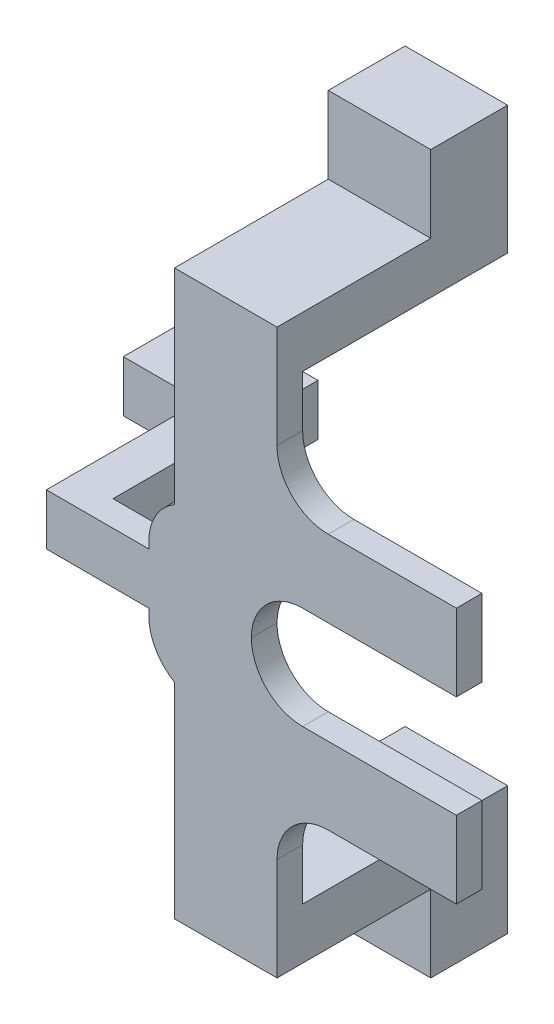
SolidWorks part; units mm, degrees
ref_plane "前视基准面" through (0, 0, 0) normal (0, 0, 1) x (1, 0, 0)
ref_plane "上视基准面" through (0, 0, 0) normal (0, 1, 0) x (1, 0, 0)
ref_plane "右视基准面" through (0, 0, 0) normal (1, 0, 0) x (0, 0, -1)
sketch "草图1" plane through (0, 0, 0) normal (0, 0, 1) x (1, 0, 0)
  line L4 (20, -10) -> (20, -0.4)
  line L5 (20, 10) -> (-20, 10)
  line L6 (-20, 10) -> (-20, 0.4)
  line L7 (-20, -10) -> (20, -10)
  line L8 (20, -0.4) -> (27, -0.4)
  line L9 (27, -0.4) -> (27, 0.4)
  line L10 (27, 0.4) -> (20, 0.4)
  line L11 (-27, -0.4) -> (-20, -0.4)
  line L12 (-27, 0.4) -> (-20, 0.4)
  line L13 (-20, 10) -> (20, -10)
  line L14 (20, 10) -> (-20, -10)
  line L15 (-27, 0.4) -> (-27, -0.4)
  line L16 (-20, -0.4) -> (-20, -10)
  line L17 (20, 0.4) -> (20, 10)
  line L19 (30, -15) -> (-30, -15)
  line L20 (30, -15) -> (30, 15)
  line L21 (30, 15) -> (-30, 15)
  line L22 (-30, -15) -> (-30, 15)
  line L23 (30, -15) -> (-30, 15) construction
  line L24 (30, 15) -> (-30, -15) construction
  point P0 (0, 0)
  point P1 (0, 0)
  dimension "D1" = 40
  dimension "D2" = 20
  dimension "D3" = 20
  dimension "D4" = 10
  dimension "D5" = 7
  dimension "D6" = 0.8
  dimension "D7" = 60
  dimension "D8" = 30
extrude "凸台-拉伸1" add sketch "草图1" along normal blind 5 contours L22 L19 L20 L21 L17 L10 L9 L8 L4 L7 L16 L11 L15 L12 L6 L5 region at (0, -14.3292, 0)
sketch "草图2" plane through (0, 0, 5) normal (0, 0, 1) x (1, 0, 0)
  line L0 (-27, 0.4) -> (-27, -0.4)
  line L1 (-27, -0.4) -> (-20, -0.4)
  line L2 (-20, -0.4) -> (-20, 0.4)
  line L3 (-20, 0.4) -> (-27, 0.4)
  line L12 (-19.8, 0.6) -> (-27.2, 0.6)
  line L13 (-27.2, 0.6) -> (-27.2, -0.6)
  line L14 (-27.2, -0.6) -> (-19.8, -0.6)
  line L15 (-19.8, -0.6) -> (-19.8, 0.6)
  line L16 (0, 0) -> (0, 5.1625) construction
  line L17 (19.8, -0.6) -> (19.8, 0.6)
  line L18 (27.2, -0.6) -> (19.8, -0.6)
  line L19 (27.2, 0.6) -> (27.2, -0.6)
  line L20 (19.8, 0.6) -> (27.2, 0.6)
  line L21 (20, 0.4) -> (27, 0.4)
  line L22 (20, -0.4) -> (20, 0.4)
  line L23 (27, -0.4) -> (20, -0.4)
  line L24 (27, 0.4) -> (27, -0.4)
  dimension "D1" = 0.2
extrude "切除-拉伸1" cut sketch "草图2" against normal blind 10
sketch "草图3" plane through (0, 0, 5) normal (0, 0, 1) x (1, 0, 0)
  line L0 (-20, 10) -> (-20, -10)
  line L1 (-20, -10) -> (20, -10)
  line L2 (20, -10) -> (20, 10)
  line L3 (20, 10) -> (-20, 10)
  line L4 (20.2, 10.2) -> (-20.2, 10.2)
  line L5 (-20.2, 10.2) -> (-20.2, -10.2)
  line L6 (-20.2, -10.2) -> (20.2, -10.2)
  line L7 (20.2, -10.2) -> (20.2, 10.2)
  dimension "D1" = 0.2
extrude "切除-拉伸2" cut sketch "草图3" against normal blind 10
sketch "草图5" plane through (0, 0, 0) normal (0, 0, -1) x (-1, 0, 0)
  line L0 (5, 15) -> (5, 55)
  line L1 (-30, 15) -> (30, 15) construction
  line L2 (30, -15) -> (30, 15) construction
  line L3 (30, 0) -> (44.4232, 0) construction
  line L4 (5, 55) -> (25, 55)
  line L6 (25, 55) -> (25, 15)
  line L7 (25, 15) -> (5, 15)
  line L8 (25, -15) -> (5, -15)
  line L9 (25, -55) -> (25, -15)
  line L10 (5, -55) -> (25, -55)
  line L11 (5, -15) -> (5, -55)
  line L12 (30, 0) -> (50, 0) construction
  line L13 (50, -5) -> (50, 5)
  line L14 (50, 5) -> (30, 5)
  line L15 (50, -5) -> (30, -5)
  line L16 (30, 5) -> (30, -5)
  point P18 (50, 0)
  dimension "D1" = 25
  dimension "D2" = 55
  dimension "D3" = 20
  dimension "D4" = 40
  dimension "D5" = 20
  dimension "D6" = 10
extrude "凸台-拉伸2" add sketch "草图5" against normal blind 5
sketch "草图6" plane through (0, 0, 0) normal (0, 0, -1) x (-1, 0, 0)
  line L0 (25, 15) -> (25, 55) construction
  line L1 (5, 55) -> (25, 55)
  line L2 (5, 55) -> (5, 45)
  line L3 (5, 45) -> (25, 45)
  line L4 (25, 55) -> (25, 45)
  line L5 (27.2, 0) -> (34.9251, 0) construction
  line L6 (27.2, 0.6) -> (27.2, -0.6) construction
  line L7 (25, -55) -> (25, -45)
  line L8 (5, -45) -> (25, -45)
  line L9 (5, -55) -> (5, -45)
  line L10 (5, -55) -> (25, -55)
  line L11 (25, 55) -> (5, 55) construction
  line L12 (50, 5) -> (50, -5)
  line L13 (50, -5) -> (50, 5) construction
  line L14 (50, 5) -> (30, 5) construction
  line L15 (50, -5) -> (42, -5)
  line L16 (30, -5) -> (50, -5) construction
  line L17 (42, -5) -> (42, 5)
  line L18 (42, 5) -> (50, 5)
  line L19 (5, -15) -> (5, -55) construction
  dimension "D1" = 90
  dimension "D2" = 8
extrude "凸台-拉伸3" add sketch "草图6" along normal blind 40
sketch "草图7" plane through (0, 0, -40) normal (0, 0, -1) x (-1, 0, 0)
  line L0 (27.2, 0) -> (32.2152, 0) construction
  line L1 (27.2, 0.6) -> (27.2, -0.6) construction
  line L2 (5, 55) -> (5, 70)
  line L3 (5, 70) -> (25, 70)
  line L4 (25, 70) -> (25, 55)
  line L5 (25, 45) -> (25, 55) construction
  line L6 (25, 55) -> (5, 55) construction
  line L7 (25, 55) -> (5, 55)
  line L8 (25, -55) -> (5, -55)
  line L9 (25, -70) -> (25, -55)
  line L10 (5, -70) -> (25, -70)
  line L11 (5, -55) -> (5, -70)
  line L12 (50, 5) -> (50, -5)
  line L13 (50, -5) -> (50, 5) construction
  line L14 (42, -5) -> (50, -5) construction
  line L15 (50, -5) -> (65, -5)
  line L16 (65, -5) -> (65, 5)
  line L17 (65, 5) -> (50, 5)
  line L18 (5, 55) -> (5, 45) construction
  dimension "D1" = 15
  dimension "D2" = 15
extrude "凸台-拉伸4" add sketch "草图7" against normal blind 15
sketch "草图8" plane through (0, 0, 5) normal (0, 0, 1) x (1, 0, 0)
  line L1 (27.466, -12.3413) -> (-27.466, -12.3413)
  line L2 (27.466, -12.3413) -> (27.466, 12.3413)
  line L3 (27.466, 12.3413) -> (-27.466, 12.3413)
  line L4 (-27.466, -12.3413) -> (-27.466, 12.3413)
  line L5 (27.466, -12.3413) -> (-27.466, 12.3413) construction
  line L6 (27.466, 12.3413) -> (-27.466, -12.3413) construction
  point P0 (0, 0)
extrude "凸台-拉伸5" add sketch "草图8" against normal blind 5
sketch "草图9" plane through (0, 0, 5) normal (0, 0, 1) x (1, 0, 0)
  line L0 (0, -10) -> (0, 10) construction
  line L1 (-10, 10) -> (30, 10)
  line L2 (30, -15) -> (30, 15) construction
  line L3 (-10, 10) -> (-10, -10)
  line L4 (-10, -10) -> (30, -10)
  line L5 (30, -10) -> (30, 10)
  point P4 (0, 0)
  dimension "D1" = 20
  dimension "D2" = 40
extrude "切除-拉伸3" cut sketch "草图9" against normal blind 5
sketch "草图10" plane through (0, 0, 5) normal (0, 0, 1) x (1, 0, 0)
  line L0 (30, 15) -> (30, 25)
  line L1 (30, 25) -> (-5, 25)
  line L2 (-5, 55) -> (-5, 15) construction
  line L3 (-5, 25) -> (-5, 15)
  line L4 (30, -15) -> (30, -25)
  line L5 (30, -25) -> (-5, -25)
  line L6 (-5, -15) -> (-5, -55) construction
  line L7 (-5, -25) -> (-5, -15)
  line L8 (-5, -15) -> (30, -15)
  line M5 (30, 15) -> (-5, 15)
  line M6 (-5, 15) -> (-5, 55)
  line M18 (-5, -55) -> (-5, -15)
  line M19 (-5, -15) -> (30, -15)
  dimension "D1" = 10
  dimension "D2" = 10
extrude "凸台-拉伸6" add sketch "草图10" against normal blind 5 contours L0 L1 M6 M5 | L5 L4 M19 M18 region at (12.5, 20, 5) region at (12.5, -20, 5)
fillet "圆角2" radius 10 4 edges at (-10, -10, 2.5) (-10, 10, 2.5) (-5, -25, 2.5) (-5, 25, 2.5)
fillet "圆角3" radius 10 2 edges at (-30, -15, 2.5) (-30, 15, 2.5)
